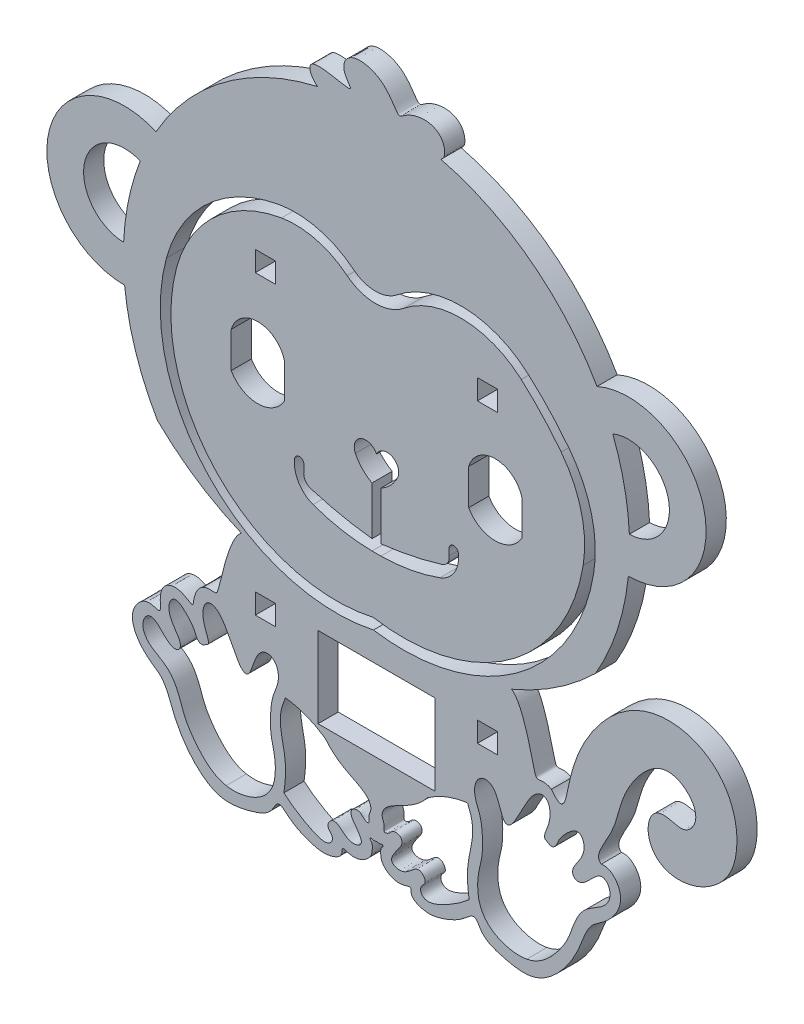
SolidWorks part; units mm, degrees
ref_plane "Front Plane" through (0, 0, 0) normal (0, 0, 1) x (1, 0, 0)
ref_plane "Top Plane" through (0, 0, 0) normal (0, 1, 0) x (1, 0, 0)
ref_plane "Right Plane" through (0, 0, 0) normal (1, 0, 0) x (0, 0, -1)
sketch "Model" plane through (0, 0, 0) normal (0, 0, 1) x (1, 0, 0)
  line L0 (-333.0845, 428.2584) -> (-333.0845, 436.6634)
  line L1 (-320.6131, 436.6634) -> (-320.6131, 428.2584)
  line L2 (-320.6131, 428.2584) -> (-333.0845, 428.2584)
  line L3 (-354.7776, 458.8961) -> (-354.7776, 497.7106)
  line L4 (-333.0845, 436.6634) -> (-320.6131, 436.6634)
  line L5 (-354.7776, 458.8961) -> (-354.7776, 335.5834) construction
  line L6 (-353.7327, 410.5736) -> (-353.7327, 408.063)
  line L7 (-353.7327, 408.063) -> (-355.8225, 408.063)
  line L8 (-355.8225, 408.063) -> (-355.8225, 410.5736)
  line L9 (-355.8225, 410.5736) -> (-355.8225, 421.9318)
  line L10 (-353.7327, 421.9318) -> (-353.7327, 410.5736)
  line L11 (-376.4707, 436.6634) -> (-388.9421, 436.6634)
  line L12 (-388.9421, 436.6634) -> (-388.9421, 428.2584)
  line L13 (-388.9421, 428.2584) -> (-376.4707, 428.2584)
  line L14 (-376.4707, 428.2584) -> (-376.4707, 436.6634)
  line L15 (-355.8225, 410.5736) -> (-355.8225, 421.9318)
  line L16 (-368.5276, 390.0306) -> (-368.5276, 362.0306) construction
  line L17 (-368.5276, 390.0306) -> (-341.0276, 390.0306) construction
  line L18 (-354.7776, 390.0306) -> (-354.7776, 362.0306) construction
  line L29 (-354.7776, 398.6237) -> (-354.7776, 368.9362) construction
  line L30 (-368.5276, 362.0306) -> (-341.0276, 362.0306) construction
  line L31 (-341.0276, 390.0306) -> (-341.0276, 362.0306) construction
  line L34 (-368.5276, 385.5306) -> (-341.0276, 385.5306)
  line L35 (-354.7776, 385.5306) -> (-354.7776, 366.5306)
  line L36 (-368.5276, 366.5306) -> (-341.0276, 366.5306)
  line L37 (-341.0276, 385.5306) -> (-341.0276, 366.5306)
  line L38 (-368.5276, 385.5306) -> (-368.5276, 366.5306)
  line L39 (-378.5276, 381.2806) -> (-383.2776, 381.2806) construction
  line L40 (-378.5276, 386.0306) -> (-378.5276, 381.2806) construction
  line L41 (-383.2776, 386.0306) -> (-383.2776, 381.2806) construction
  line L42 (-378.5276, 386.0306) -> (-383.2776, 386.0306) construction
  line L43 (-331.0276, 381.2806) -> (-326.2776, 381.2806) construction
  line L44 (-331.0276, 386.0306) -> (-331.0276, 381.2806) construction
  line L45 (-326.2776, 386.0306) -> (-326.2776, 381.2806) construction
  line L46 (-331.0276, 386.0306) -> (-326.2776, 386.0306) construction
  line L47 (-378.5276, 381.2806) -> (-383.2776, 381.2806)
  line L48 (-378.5276, 386.0306) -> (-378.5276, 381.2806)
  line L49 (-383.2776, 386.0306) -> (-383.2776, 381.2806)
  line L50 (-378.5276, 386.0306) -> (-383.2776, 386.0306)
  line L51 (-331.0276, 381.2806) -> (-326.2776, 381.2806)
  line L52 (-331.0276, 386.0306) -> (-331.0276, 381.2806)
  line L53 (-326.2776, 386.0306) -> (-326.2776, 381.2806)
  line L54 (-331.0276, 386.0306) -> (-326.2776, 386.0306)
  line L55 (-326.2776, 451.0306) -> (-331.0276, 451.0306)
  line L56 (-383.2776, 455.7806) -> (-378.5276, 455.7806)
  line L57 (-383.2776, 455.7806) -> (-383.2776, 451.0306)
  line L58 (-383.2776, 451.0306) -> (-378.5276, 451.0306)
  line L59 (-378.5276, 455.7806) -> (-378.5276, 451.0306)
  line L60 (-331.0276, 455.7806) -> (-331.0276, 451.0306)
  line L61 (-326.2776, 455.7806) -> (-331.0276, 455.7806)
  line L62 (-326.2776, 455.7806) -> (-326.2776, 451.0306)
  arc A0 (-335.5443, 417.8482) -> (-337.6917, 417.8482) centre (-336.618, 417.6887) ccw
  arc A1 (-353.8616, 408.063) -> (-339.8605, 410.5951) centre (-354.2026, 449.9227) ccw
  arc A2 (-337.6917, 417.8482) -> (-337.6917, 416.1744) centre (-332.0588, 417.0113) ccw
  arc A3 (-333.0845, 428.2584) -> (-320.6131, 428.2584) centre (-326.8488, 431.7805) ccw
  arc A4 (-339.8605, 410.5951) -> (-335.5443, 417.8482) centre (-342.1478, 416.8671) ccw
  arc A5 (-339.3452, 413.5564) -> (-337.6917, 416.1744) centre (-340.0388, 415.8257) ccw
  arc A6 (-353.7327, 410.5736) -> (-339.3452, 413.5564) centre (-362.6634, 489.8421) ccw
  circle A7 centre (-295.506, 451.3512) radius 18.2563
  arc A8 (-376.4707, 436.6634) -> (-388.9421, 436.6634) centre (-382.7064, 434.8602) ccw
  arc A9 (-388.9421, 428.2584) -> (-376.4707, 428.2584) centre (-382.7064, 431.7805) ccw
  circle A10 centre (-295.506, 451.3512) radius 9.6191
  arc A11 (-369.6946, 410.5951) -> (-355.6936, 408.063) centre (-355.3526, 449.9227) ccw
  arc A12 (-371.8635, 417.8482) -> (-374.0109, 417.8482) centre (-372.9372, 417.6887) ccw
  arc A13 (-371.8635, 416.1744) -> (-370.21, 413.5564) centre (-369.5164, 415.8257) ccw
  arc A14 (-370.21, 413.5564) -> (-355.8225, 410.5736) centre (-346.8918, 489.8421) ccw
  circle A15 centre (-414.0491, 451.3512) radius 9.6191
  arc A16 (-374.0109, 417.8482) -> (-369.6946, 410.5951) centre (-367.4074, 416.8671) ccw
  arc A17 (-371.8635, 416.1744) -> (-371.8635, 417.8482) centre (-377.4964, 417.0113) ccw
  circle A18 centre (-414.0491, 451.3512) radius 18.2562
  arc A19 (-404.1865, 443.5481) -> (-355.495, 392.1367) centre (-364.1697, 432.6844) ccw
  arc A20 (-377.544, 467.7237) -> (-404.1865, 443.5481) centre (-371.9573, 434.7986) ccw
  arc A21 (-360.1092, 463.1724) -> (-377.544, 467.7237) centre (-373.8759, 446.1059) ccw
  arc A22 (-360.1092, 463.1724) -> (-349.9379, 463.1724) centre (-355.0236, 469.4771) ccw
  arc A23 (-319.0661, 462.4148) -> (-349.9379, 463.1724) centre (-334.9487, 444.5903) ccw
  arc A24 (-309.3551, 451.9861) -> (-319.0661, 462.4148) centre (-370.017, 405.2343) ccw
  arc A25 (-303.7017, 429.5427) -> (-309.3551, 451.9861) centre (-332.3576, 434.2582) ccw
  arc A26 (-355.495, 392.1367) -> (-303.7017, 429.5427) centre (-348.4206, 436.9015) ccw
  arc A27 (-320.6131, 436.6634) -> (-333.0845, 436.6634) centre (-326.8488, 434.8602) ccw
  arc A28 (-359.7442, 426.0052) -> (-355.8225, 421.9318) centre (-351.6275, 429.895) ccw
  arc A29 (-354.7776, 428.3148) -> (-359.7442, 426.0052) centre (-357.2743, 427.1889) ccw
  arc A30 (-349.811, 426.0052) -> (-354.7776, 428.3148) centre (-352.2809, 427.1889) ccw
  arc A31 (-353.7327, 421.9318) -> (-349.811, 426.0052) centre (-357.9277, 429.895) ccw
  arc A33 (-303.2483, 409.4214) -> (-354.7776, 497.7106) centre (-353.9365, 439.0196) ccw
  arc A34 (-354.7776, 497.7106) -> (-406.3069, 409.4214) centre (-355.6187, 439.0196) ccw
  arc A36 (-320.7293, 460.5483) -> (-348.3683, 461.2266) centre (-334.9487, 444.5903) ccw
  arc A37 (-361.6788, 461.2266) -> (-348.3683, 461.2266) centre (-355.0236, 469.4771) ccw
  arc A38 (-361.6788, 461.2266) -> (-377.1258, 465.259) centre (-373.8759, 446.1059) ccw
  arc A39 (-377.1258, 465.259) -> (-401.7738, 442.8932) centre (-371.9573, 434.7986) ccw
  arc A40 (-401.7738, 442.8932) -> (-355.5644, 394.6813) centre (-364.1697, 432.6844) ccw
  arc A41 (-355.5644, 394.6813) -> (-306.1685, 429.9486) centre (-348.4206, 436.9015) ccw
  arc A42 (-306.1685, 429.9486) -> (-311.3352, 450.4601) centre (-332.3576, 434.2582) ccw
  arc A43 (-311.3352, 450.4601) -> (-320.7293, 460.5483) centre (-370.017, 405.2343) ccw
  spline S0 degree 5 number of poles 191 (-386.5513, 396.3273) -> (-354.7776, 349.4226)
  spline S1 degree 5 poles (-392.3003, 381.4192) (-392.2041, 381.237) (-392.0138, 380.8984) (-391.7346, 380.4672) (-391.3751, 380.0459) (-390.9436, 379.7562) (-390.5211, 379.6479) (-390.0888, 379.6039) (-389.524, 379.4129) (-388.868, 378.8022) (-388.1129, 377.5986) (-387.3489, 376.0745) (-386.6772, 374.6518) (-386.2179, 373.7446) (-385.8731, 373.2785) (-385.6145, 373.315) (-385.3631, 373.7767) (-385.0271, 374.5143) (-384.5404, 375.3692) (-383.8806, 376.2108) (-383.0551, 376.931) (-382.0944, 377.4495) (-381.0439, 377.715) (-379.9549, 377.7079) (-378.8773, 377.4424) (-377.8577, 376.9567) (-376.9382, 376.3028) (-376.155, 375.5371) (-375.5367, 374.7103) (-375.103, 373.8568) (-374.8634, 372.9898) (-374.8163, 372.1089) (-374.9481, 371.2048) (-375.2326, 370.2656) (-375.6291, 369.2822) (-376.0847, 368.2517) (-376.542, 367.1753) (-376.9451, 366.0569) (-377.2465, 364.9023) (-377.4137, 363.7179) (-377.4409, 362.2675) (-377.2741, 360.7867) (-376.978, 359.2821) (-376.6492, 357.7606) (-376.3743, 356.2331) (-376.2147, 354.9637) (-376.1402, 353.7082) (-376.1481, 352.4796) (-376.2233, 351.2923) (-376.3425, 350.1608) (-376.4787, 349.0988) (-376.6058, 348.1181) (-376.7231, 347.0492) (-376.7695, 346.277) (-376.7675, 345.7376) (-376.7441, 345.377) (-376.7187, 345.1562) knots 0 0 0 0 0 0 0.018182 0.036364 0.054545 0.072727 0.090909 0.109091 0.127273 0.163636 0.181818 0.2 0.218182 0.236364 0.254545 0.272727 0.290909 0.309091 0.327273 0.345455 0.363636 0.381818 0.4 0.418182 0.436364 0.454545 0.472727 0.490909 0.509091 0.527273 0.545455 0.563636 0.581818 0.6 0.618182 0.636364 0.654545 0.672727 0.690909 0.709091 0.727273 0.763636 0.781818 0.8 0.818182 0.836364 0.854545 0.872727 0.890909 0.909091 0.927273 0.945455 0.963636 1 1 1 1 1 1 weights 1 1 1 1 1 1 1 1 1 1 1 1 1 1 1 1 1 1 1 1 1 1 1 1 1 1 1 1 1 1 1 1 1 1 1 1 1 1 1 1 1 1 1 1 1 1 1 1 1 1 1 1 1 1 1 1 1
  spline S2 degree 5 poles (-317.2549, 381.4192) (-317.3511, 381.237) (-317.5414, 380.8984) (-317.8205, 380.4672) (-318.1801, 380.0459) (-318.6116, 379.7562) (-319.0341, 379.6479) (-319.4664, 379.6039) (-320.0312, 379.4129) (-320.6872, 378.8022) (-321.4423, 377.5986) (-322.2063, 376.0745) (-322.878, 374.6518) (-323.3372, 373.7446) (-323.682, 373.2785) (-323.9407, 373.315) (-324.192, 373.7767) (-324.5281, 374.5143) (-325.0148, 375.3692) (-325.6745, 376.2108) (-326.5001, 376.931) (-327.4607, 377.4495) (-328.5113, 377.715) (-329.6003, 377.7079) (-330.6779, 377.4424) (-331.6975, 376.9567) (-332.617, 376.3028) (-333.4002, 375.5371) (-334.0185, 374.7103) (-334.4522, 373.8568) (-334.6918, 372.9898) (-334.7389, 372.1089) (-334.6071, 371.2048) (-334.3226, 370.2656) (-333.9261, 369.2822) (-333.4705, 368.2517) (-333.0132, 367.1753) (-332.6101, 366.0569) (-332.3086, 364.9023) (-332.1415, 363.7179) (-332.1143, 362.2675) (-332.2811, 360.7867) (-332.5772, 359.2821) (-332.906, 357.7606) (-333.1809, 356.2331) (-333.3405, 354.9637) (-333.415, 353.7082) (-333.4071, 352.4796) (-333.3318, 351.2923) (-333.2127, 350.1608) (-333.0765, 349.0988) (-332.9494, 348.1181) (-332.8321, 347.0492) (-332.7857, 346.277) (-332.7877, 345.7376) (-332.8111, 345.377) (-332.8364, 345.1562) knots 0 0 0 0 0 0 0.018182 0.036364 0.054545 0.072727 0.090909 0.109091 0.127273 0.163636 0.181818 0.2 0.218182 0.236364 0.254545 0.272727 0.290909 0.309091 0.327273 0.345455 0.363636 0.381818 0.4 0.418182 0.436364 0.454545 0.472727 0.490909 0.509091 0.527273 0.545455 0.563636 0.581818 0.6 0.618182 0.636364 0.654545 0.672727 0.690909 0.709091 0.727273 0.763636 0.781818 0.8 0.818182 0.836364 0.854545 0.872727 0.890909 0.909091 0.927273 0.945455 0.963636 1 1 1 1 1 1 weights 1 1 1 1 1 1 1 1 1 1 1 1 1 1 1 1 1 1 1 1 1 1 1 1 1 1 1 1 1 1 1 1 1 1 1 1 1 1 1 1 1 1 1 1 1 1 1 1 1 1 1 1 1 1 1 1 1
  spline S3 degree 5 number of poles 191 (-323.0039, 396.3273) -> (-354.7776, 349.4226)
  spline S4 degree 5 poles (-383.9314, 395.3059) (-384.0217, 395.2303) (-384.2065, 395.0559) (-384.4966, 394.7244) (-384.9096, 394.1402) (-385.4718, 393.1605) (-386.0823, 391.9186) (-386.7412, 390.4138) (-387.4448, 388.6659) (-388.1884, 386.7006) (-388.9674, 384.5433) (-389.6159, 382.6802) (-390.1154, 381.2113) (-390.4542, 380.2006) (-390.625, 379.6875) knots 0 0 0 0 0 0 0.1 0.2 0.3 0.4 0.5 0.6 0.7 0.8 0.9 1 1 1 1 1 1 weights 1 1 1 1 1 1 1 1 1 1 1 1 1 1 1
  spline S5 degree 5 poles (-324.9742, 395.5465) (-324.9075, 395.5713) (-324.7671, 395.586) (-324.536, 395.5034) (-324.186, 395.1803) (-323.6758, 394.4059) (-323.0908, 393.2508) (-322.4348, 391.7339) (-321.7151, 389.8927) (-320.9398, 387.7682) (-320.1161, 385.3979) (-319.423, 383.3273) (-318.8854, 381.6837) (-318.5192, 380.5484) (-318.3341, 379.9708) knots 0 0 0 0 0 0 0.1 0.2 0.3 0.4 0.5 0.6 0.7 0.8 0.9 1 1 1 1 1 1 weights 1 1 1 1 1 1 1 1 1 1 1 1 1 1 1
  spline S6 degree 5 number of poles 87 (-390.131, 343.1251) -> (-394.9344, 369.4271)
  spline S7 degree 5 number of poles 87 (-394.9344, 369.4271) -> (-390.131, 343.1251)
  spline S8 degree 5 number of poles 87 (-319.4242, 343.1251) -> (-314.6207, 369.4271)
  spline S9 degree 5 number of poles 87 (-314.6207, 369.4271) -> (-319.4242, 343.1251)
  spline S10 degree 5 number of poles 100 (-313.6608, 380.6036) -> (-301.8989, 371.25)
  spline S11 degree 3 poles (-303.2483, 409.4214) (-316.9313, 395.9718) (-336.2317, 389.4535) (-355.495, 392.1367) knots 0 0 0 0 1 1 1 1
  spline S12 degree 3 poles (-325.8189, 391.6517) (-325.0433, 389.943) (-323.9731, 387.0385) (-322.3233, 382.144) (-321.826, 380.6276) (-321.3101, 379.0173) knots 0.415933 0.415933 0.415933 0.415933 0.831377 0.831377 1 1 1 1
  spline S13 degree 3 poles (-382.8373, 391.4106) (-378.9959, 389.8402) (-375.2195, 388.9079) (-367.7502, 388.2248) (-364.1525, 388.5138) (-357.4032, 388.957) (-354.179, 389.0839) (-345.6505, 389.037) (-340.1418, 388.7675) (-331.7579, 389.7039) (-328.6238, 390.4478) (-325.8189, 391.6517) knots 0.037902 0.037902 0.037902 0.037902 0.218565 0.218565 0.406397 0.406397 0.567357 0.567357 0.800191 0.800191 0.954811 0.954811 0.954811 0.954811
  spline S14 degree 3 poles (-382.8373, 391.4106) (-383.8297, 389.4643) (-385.2631, 385.732) (-387.1031, 380.3617) (-387.3791, 379.5442) (-387.66, 378.7004) knots 0.323206 0.323206 0.323206 0.323206 0.900399 0.900399 1 1 1 1
  spline S15 degree 5 poles (-387.66, 378.7004) (-387.7294, 378.4251) (-387.7988, 378.1499) (-387.8682, 377.8746) (-387.9376, 377.5994) (-388.007, 377.3241) knots 0 0 0 0 0 0 1 1 1 1 1 1 weights 1 1 1 1 1 1
  spline S16 degree 5 poles (-321.3101, 379.0173) (-321.2632, 378.8383) (-321.2162, 378.6593) (-321.1693, 378.4803) (-321.1224, 378.3013) (-321.0754, 378.1223) knots 0 0 0 0 0 0 1 1 1 1 1 1 weights 1 1 1 1 1 1
  spline S17 degree 5 number of poles 138 (-376.5625, 348.4375) -> (-354.7776, 358.6225)
  spline S18 degree 5 number of poles 138 (-332.9927, 348.4375) -> (-354.7776, 358.6225)
  spline S19 degree 5 number of poles 65 (-368.6485, 496.2522) -> (-339.8111, 495.9917)
  spline S22 degree 3 poles (-406.3069, 409.4214) (-392.9644, 396.349) (-374.2799, 389.6792) (-355.495, 392.1367) knots 0 0 0 0 1 1 1 1
  spline S23 degree 2 poles (-342.7628, 364.3505) (-338.4944, 367.3534) (-333.3581, 367.9777) knots 0 0 0 1 1 1
  spline S25 degree 2 poles (-366.7924, 364.3505) (-371.0608, 367.3534) (-376.1971, 367.9777) knots 0 0 0 1 1 1
  dimension "D1" = 28
  dimension "D2" = 13.75
  dimension "D3" = 107.68
  dimension "D4" = 4.5
  dimension "D5" = 4.5
  dimension "D6" = 65
extrude "Boss-Extrude1" add sketch "Model" along normal blind 4.75 contours A7 A33 L3 A22 A23 A24 | S19 A34 A33 | L3 A34 A18 A20 A21 A22 | A10 A33 A7 A24 A25 | A10 A33 | A33 A10 A7 | S11 A33 A7 A25 A26 | A34 A18 A15 | A18 A34 A15 A19 A20 | A15 A34 | A34 S22 A19 A18 | A7 A43 A36 A37 A38 A39 A18 A40 A41 A42 A31 L10 A6 A5 A2 A0 A4 A1 L6 L7 L8 A11 A16 A12 A17 A13 A14 L9 A28 A29 A30 A27 L1 A3 L0 A9 L12 A8 L14 | A39 A40 A18 | A42 A43 A7 | S10 S3 | S22 S4 S1 S15 S14 S13 S12 S16 S2 S5 S11 A26 A19 | S3 S11 S5 S2 | S22 S0 S1 S4 | S1 S0 S6 S7 | S10 S3 S2 S9 S8 | S25 S17 L36 L38 L34 L37 S18 S23 S2 S16 S12 S13 S14 S15 S1 | S17 L38 | L37 S18 | L38 S17 | S18 L37 | S18 L36 S17 | S2 S18 L36 S17 S1 S0 S3 region at (-376.2416, 478.2135, 0) region at (-333.2361, 478.2724, 0) region at (-354.5371, 500.3437, 0) region at (-301.2701, 464.0338, 0) region at (-285.798, 466.2827, 0) region at (-409.0425, 464.3935, 0) region at (-400.8426, 463.3824, 0) region at (-300.18, 450.3648, 0) region at (-404.0152, 416.6036, 0) region at (-409.3752, 450.3648, 0) region at (-355.0507, 430.1684, 0) region at (-398.9985, 445.39, 0) region at (-310.1131, 444.6099, 0) region at (-308.1368, 414.0587, 0) region at (-354.5711, 389.3864, 0) region at (-388.6481, 388.7743, 0) region at (-320.5369, 388.9651, 0) region at (-392.0614, 380.0199, 0) region at (-315.472, 380.609, 0) region at (-354.7776, 351.3875, 0) region at (-387.1326, 377.8355, 0) region at (-274.0272, 382.186, 0) region at (-354.7776, 364.0887, 0) region at (-369.5479, 376.9973, 0) region at (-368.6184, 376.0399, 0) region at (-340.0073, 376.9973, 0) region at (-340.9368, 376.0399, 0)
